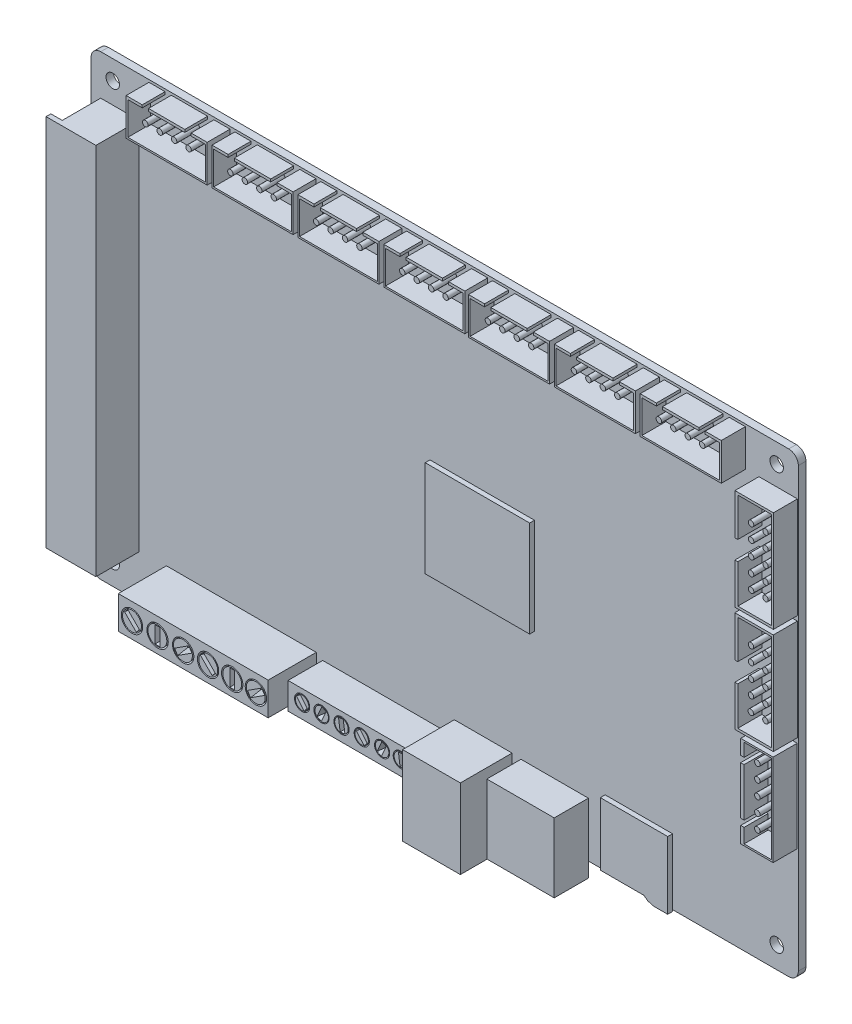
SolidWorks part; units mm, degrees
ref_plane "Front Plane" through (0, 0, 0) normal (0, 0, 1) x (1, 0, 0)
ref_plane "Top Plane" through (0, 0, 0) normal (0, 1, 0) x (1, 0, 0)
ref_plane "Right Plane" through (0, 0, 0) normal (1, 0, 0) x (0, 0, -1)
sketch "Sketch3" plane through (0, 0, 0) normal (0, 0, 1) x (1, 0, 0)
  line L1 (-56.2922, 43.8866) -> (90.7078, 43.8866)
  line L2 (-56.2922, 43.8866) -> (-56.2922, -51.1134)
  line L3 (-56.2922, -51.1134) -> (90.7078, -51.1134)
  line L4 (90.7078, 43.8866) -> (90.7078, -51.1134)
  dimension "D1" = 147
  dimension "D2" = 95
extrude "Boss-Extrude5" add sketch "Sketch3" along normal blind 1.5748 contours L1 L4 L3 L2
sketch "Sketch6" plane through (0, 0, 1.5748) normal (0, 0, 1) x (1, 0, 0)
  line L0 (-56.2922, 43.8866) -> (-56.2922, -51.1134) construction
  line L1 (-56.2922, -51.1134) -> (90.7078, -51.1134) construction
  line L2 (90.7078, 43.8866) -> (90.7078, -51.1134) construction
  circle A7 centre (-51.7922, -46.6134) radius 1.4
  circle A8 centre (-51.7922, 39.8866) radius 1.4
  circle A9 centre (86.2078, -46.6134) radius 1.4
  circle A10 centre (86.2078, 39.8866) radius 1.4
  dimension "D3" = 4.5
  dimension "D5" = 138
  dimension "D1" = 2.8
  dimension "D2" = 4.5
  dimension "D4" = 86.5
  dimension "D6" = 4.5
  dimension "D7" = 4.5
extrude "Cut-Extrude2" cut sketch "Sketch6" against normal blind 1.5748 contours A8 | A9 | A7 | A10
fillet "Fillet6" radius 2 4 edges at (-56.2922, -51.1134, 0.7874) (90.7078, -51.1134, 0.7874) (-56.2922, 43.8866, 0.7874) (90.7078, 43.8866, 0.7874)
sketch "Sketch15" plane through (0, 0, 1.5748) normal (0, 0, 1) x (1, 0, 0)
  line L1 (14.1477, 4.6258) -> (35.8627, 4.6258)
  line L2 (14.1477, 4.6258) -> (14.1477, -15.3707)
  line L3 (14.1477, -15.3707) -> (35.8627, -15.3707)
  line L4 (35.8627, 4.6258) -> (35.8627, -15.3707)
extrude "Boss-Extrude10" add sketch "Sketch15" along normal blind 1
sketch "Sketch7" plane through (0, 0, 1.5748) normal (0, 0, 1) x (1, 0, 0)
  line L0 (-54.2922, -51.1134) -> (88.7078, -51.1134) construction
  line L1 (19.2078, -39.6134) -> (31.2078, -39.6134)
  line L2 (19.2078, -39.6134) -> (19.2078, -56.1134)
  line L3 (19.2078, -56.1134) -> (31.2078, -56.1134)
  line L4 (31.2078, -39.6134) -> (31.2078, -56.1134)
  line L5 (-56.2922, 41.8866) -> (-56.2922, -49.1134) construction
  point P4 (25.2078, -39.6134)
  dimension "D1" = 16.5
  dimension "D2" = 12
  dimension "D3" = 5
  dimension "D4" = 75.5
extrude "Boss-Extrude6" add sketch "Sketch7" along normal blind 10.75
sketch "Sketch8" plane through (0, -56.1134, 0) normal (0, -1, 0) x (-1, 0, 0)
  line L0 (-22.3419, -10.6751) -> (-27.8419, -10.6751)
  line L1 (-22.3419, -10.6751) -> (-20.7873, -9.2035)
  line L2 (-27.8419, -10.6751) -> (-29.2373, -9.2011)
  line L3 (-20.7873, -9.2035) -> (-20.7873, -2.8951)
  line L4 (-20.7873, -2.8951) -> (-29.2373, -2.8951)
  line L5 (-29.2373, -2.8951) -> (-29.2373, -9.2011)
  dimension "D1" = 8.45
  dimension "D2" = 7.78
  dimension "D3" = 5.5
extrude "Cut-Extrude3" cut sketch "Sketch8" against normal blind 12
sketch "Sketch9" plane through (0, -44.1134, 0) normal (0, -1, 0) x (-1, 0, 0)
  line L1 (-22.3046, -8.5212) -> (-27.8046, -8.5212)
  line L2 (-22.3046, -8.5212) -> (-22.3046, -5.4712)
  line L3 (-22.3046, -5.4712) -> (-27.8046, -5.4712)
  line L4 (-27.8046, -8.5212) -> (-27.8046, -5.4712)
  dimension "D1" = 3.05
  dimension "D2" = 5.5
extrude "Boss-Extrude7" add sketch "Sketch9" along normal blind 11
sketch "Sketch10" plane through (0, 0, 1.5748) normal (0, 0, 1) x (1, 0, 0)
  line L1 (33.0644, -39.8012) -> (47.0644, -39.8012)
  line L2 (33.0644, -39.8012) -> (33.0644, -54.2012)
  line L3 (33.0644, -54.2012) -> (47.0644, -54.2012)
  line L4 (47.0644, -39.8012) -> (47.0644, -54.2012)
  dimension "D1" = 14.4
  dimension "D2" = 14
extrude "Boss-Extrude8" add sketch "Sketch10" along normal blind 7.1
sketch "Sketch13" plane through (0, -54.2012, 0) normal (0, -1, 0) x (1, 0, 0)
  line L1 (33.801, 7.7215) -> (46.301, 7.7215)
  line L2 (33.801, 7.7215) -> (33.801, 2.6215)
  line L3 (33.801, 2.6215) -> (46.301, 2.6215)
  line L4 (46.301, 7.7215) -> (46.301, 2.6215)
  dimension "D1" = 12.5
  dimension "D2" = 5.1
extrude "Cut-Extrude4" cut sketch "Sketch13" against normal blind 13.1
sketch "Sketch14" plane through (0, -41.1012, 0) normal (0, -1, 0) x (1, 0, 0)
  line L1 (34.0885, 7.335) -> (46.0885, 7.335)
  line L2 (34.0885, 7.335) -> (34.0885, 5.335)
  line L3 (34.0885, 5.335) -> (46.0885, 5.335)
  line L4 (46.0885, 7.335) -> (46.0885, 5.335)
  dimension "D1" = 12
  dimension "D2" = 2
extrude "Boss-Extrude9" add sketch "Sketch14" along normal blind 13.1
sketch "Sketch17" plane through (0, 0, 1.5748) normal (0, 0, 1) x (1, 0, 0)
  line L0 (50.553, -50.5188) -> (59.5882, -50.5188)
  line L1 (50.553, -37.4607) -> (64.553, -37.4607)
  line L2 (50.553, -37.4607) -> (50.553, -50.5188)
  line L3 (61.5418, -51.4607) -> (64.553, -51.4607)
  line L4 (64.553, -37.4607) -> (64.553, -51.4607)
  line L5 (59.5882, -50.5188) -> (60.4255, -51.1134)
  line L6 (47.0644, -51.1134) -> (88.7078, -51.1134) construction
  line L7 (60.4255, -51.1134) -> (61.5418, -51.4607)
  dimension "D1" = 14
  dimension "D2" = 14
extrude "Boss-Extrude12" add sketch "Sketch17" along normal blind 1
sketch "Sketch18" plane through (0, -50.5188, 0) normal (0, -1, 0) x (-1, 0, 0)
  line L1 (-50.8215, -2.3946) -> (-59.6018, -2.3946)
  line L2 (-50.8215, -2.3946) -> (-50.8215, -1.7409)
  line L3 (-50.8215, -1.7409) -> (-59.6018, -1.7409)
  line L4 (-59.6018, -2.3946) -> (-59.6018, -1.7409)
extrude "Cut-Extrude6" cut sketch "Sketch18" against normal blind 12
sketch "Sketch20" plane through (59.6018, 0, 0) normal (-1, 0, 0) x (0, 0, 1)
  line L0 (1.7409, -50.5188) -> (2.3946, -50.5188) construction
  line L1 (2.3635, -38.552) -> (1.7409, -38.552)
  line L2 (2.3635, -38.552) -> (2.3635, -50.5188)
  line L3 (2.3635, -50.5188) -> (1.7409, -50.5188)
  line L4 (1.7409, -38.552) -> (1.7409, -50.5188)
  line L5 (1.7409, -38.5188) -> (1.7409, -50.5188) construction
extrude "Cut-Extrude10" cut sketch "Sketch20" against normal blind 4.2
sketch "Sketch23" plane through (-3.8693, -5.4478, 0) normal (-0.5791, -0.8153, 0) x (0.8153, -0.5791, 0)
  line L0 (77.8348, 2.3946) -> (77.8348, 1.7409) construction
  line L1 (77.8348, 2.3894) -> (78.8617, 2.3894)
  line L2 (77.8348, 2.3894) -> (77.8348, 1.7571)
  line L3 (77.8348, 1.7571) -> (78.8617, 1.7571)
  line L4 (78.8617, 2.3894) -> (78.8617, 1.7571)
  line L5 (78.8617, 2.5748) -> (78.8617, 1.5748) construction
extrude "Cut-Extrude11" cut sketch "Sketch23" against normal blind 6.2
sketch "Sketch24" plane through (-9.1658, -29.4664, 0) normal (-0.297, -0.9549, 0) x (0.9549, -0.297, 0)
  line L0 (74.0494, 2.5748) -> (74.0494, 1.5748) construction
  line L1 (72.8803, 2.3894) -> (74.0494, 2.3894)
  line L2 (72.8803, 2.3894) -> (72.8803, 1.7551)
  line L3 (72.8803, 1.7551) -> (74.0494, 1.7551)
  line L4 (74.0494, 2.3894) -> (74.0494, 1.7551)
extrude "Cut-Extrude12" cut sketch "Sketch24" against normal blind 7.2
sketch "Sketch25" plane through (0, -51.4607, 0) normal (0, -1, 0) x (1, 0, 0)
  line L1 (61.5418, 2.3894) -> (64.4593, 2.3894)
  line L2 (61.5418, 2.3894) -> (61.5418, 1.7551)
  line L3 (61.5418, 1.7551) -> (64.4593, 1.7551)
  line L4 (64.4593, 2.3894) -> (64.4593, 1.7551)
extrude "Cut-Extrude13" cut sketch "Sketch25" against normal blind 12.2
sketch "Sketch26" plane through (0, 0, 1.5748) normal (0, 0, 1) x (1, 0, 0)
  line L1 (17.0307, -48.1542) -> (-8.1581, -48.1542)
  line L2 (17.0307, -48.1542) -> (17.0307, -42.6208)
  line L3 (17.0307, -42.6208) -> (-8.1581, -42.6208)
  line L4 (-8.1581, -48.1542) -> (-8.1581, -42.6208)
extrude "Boss-Extrude13" add sketch "Sketch26" along normal blind 7.2
sketch "Sketch27" plane through (0, 0, 8.7748) normal (0, 0, 1) x (1, 0, 0)
  circle A0 centre (-5.2362, -45.1806) radius 1.5803
  circle A1 centre (-1.2032, -45.1806) radius 1.5803
  circle A2 centre (2.957, -45.1806) radius 1.5803
  circle A3 centre (7.1668, -45.1908) radius 1.5803
  circle A4 centre (11.4, -45.1908) radius 1.5803
  circle A5 centre (15.2791, -45.1908) radius 1.5803
extrude "Cut-Extrude15" cut sketch "Sketch27" against normal blind 6.2
sketch "Sketch29" plane through (0, -48.1542, 0) normal (0, -1, 0) x (1, 0, 0)
  line L0 (-8.1581, 5.1748) -> (17.0307, 5.1748) construction
  line L1 (-8.1581, 8.7748) -> (-8.1581, 1.5748) construction
  line L2 (17.0307, 8.7748) -> (17.0307, 1.5748) construction
  line L3 (-7.6895, 11.9968) -> (-7.6895, 5.1748) construction
  line L4 (-3.9145, 11.9968) -> (-3.9145, 5.1748) construction
  line L5 (-3.487, 5.1563) -> (0.1391, 5.1563)
  line L6 (-7.6895, 5.1707) -> (-3.9145, 5.1707)
  line L7 (-7.6895, 5.1707) -> (-7.6895, 1.9056)
  line L8 (-7.6895, 1.9056) -> (-3.9145, 1.9056)
  line L9 (-3.9145, 5.1707) -> (-3.9145, 1.9056)
  line L10 (-3.487, 5.1563) -> (-3.487, 1.8334)
  line L11 (-3.487, 1.8334) -> (0.1391, 1.8334)
  line L12 (0.1391, 5.1563) -> (0.1391, 1.8334)
  line L13 (0.772, 5.2105) -> (4.4078, 5.2105)
  line L14 (0.772, 5.2105) -> (0.772, 1.8519)
  line L15 (0.772, 1.8519) -> (4.4078, 1.8519)
  line L16 (4.4078, 5.2105) -> (4.4078, 1.8519)
  line L17 (5.1003, 5.1709) -> (8.7885, 5.1709)
  line L18 (5.1003, 5.1709) -> (5.1003, 1.8362)
  line L19 (5.1003, 1.8362) -> (8.7885, 1.8362)
  line L20 (8.7885, 5.1709) -> (8.7885, 1.8362)
  line L21 (9.3884, 5.192) -> (12.9675, 5.192)
  line L22 (9.3884, 5.192) -> (9.3884, 1.8436)
  line L23 (9.3884, 1.8436) -> (12.9675, 1.8436)
  line L24 (12.9675, 5.192) -> (12.9675, 1.8436)
  line L25 (13.3889, 5.2027) -> (16.8771, 5.2027)
  line L26 (13.3889, 5.2027) -> (13.3889, 1.8194)
  line L27 (13.3889, 1.8194) -> (16.8771, 1.8194)
  line L28 (16.8771, 5.2027) -> (16.8771, 1.8194)
extrude "Cut-Extrude18" cut sketch "Sketch29" against normal blind 5.2
sketch "Sketch39" plane through (0, 0, 8.7748) normal (0, 0, 1) x (1, 0, 0)
  circle A0 centre (-5.2362, -45.1806) radius 1.3961
  circle A1 centre (-1.1593, -45.1806) radius 1.3961
  circle A3 centre (2.9415, -45.1806) radius 1.3961
  circle A4 centre (7.1495, -45.1806) radius 1.3961
  circle A5 centre (11.4024, -45.1806) radius 1.3961
  circle A6 centre (15.2907, -45.1806) radius 1.3961
extrude "Boss-Extrude19" add sketch "Sketch39" against normal blind 6 draft 2 separate body
sketch "Sketch89" plane through (0, -48.1542, 0) normal (0, -1, 0) x (1, 0, 0)
  line L0 (-3.9145, 1.9056) -> (-3.9145, 5.1707) construction
  line L1 (-7.6895, 5.1707) -> (-3.9145, 5.1707)
  line L2 (-7.6895, 5.1707) -> (-7.6895, 2.6391)
  line L3 (-7.6895, 2.6391) -> (-3.9145, 2.6391)
  line L4 (-3.9145, 5.1707) -> (-3.9145, 2.6391)
  line L5 (0.1391, 1.8334) -> (0.1391, 5.1563) construction
  line L6 (-3.487, 5.1563) -> (0.1391, 5.1563)
  line L7 (-3.487, 5.1563) -> (-3.487, 2.6391)
  line L8 (-3.487, 2.6391) -> (0.1391, 2.6391)
  line L9 (0.1391, 5.1563) -> (0.1391, 2.6391)
  line L10 (4.4078, 1.8519) -> (4.4078, 5.2105) construction
  line L11 (0.772, 5.2105) -> (4.4078, 5.2105)
  line L12 (0.772, 5.2105) -> (0.772, 2.6391)
  line L13 (0.772, 2.6391) -> (4.4078, 2.6391)
  line L14 (4.4078, 5.2105) -> (4.4078, 2.6391)
  line L15 (8.7885, 1.8362) -> (8.7885, 5.1709) construction
  line L16 (5.1003, 5.1709) -> (8.7885, 5.1709)
  line L17 (5.1003, 5.1709) -> (5.1003, 2.6391)
  line L18 (5.1003, 2.6391) -> (8.7885, 2.6391)
  line L19 (8.7885, 5.1709) -> (8.7885, 2.6391)
  line L20 (12.9675, 1.8436) -> (12.9675, 5.192) construction
  line L21 (9.3884, 5.192) -> (12.9675, 5.192)
  line L22 (9.3884, 5.192) -> (9.3884, 2.6451)
  line L23 (9.3884, 2.6451) -> (12.9675, 2.6451)
  line L24 (12.9675, 5.192) -> (12.9675, 2.6451)
  line L25 (16.8771, 1.8194) -> (16.8771, 5.2027) construction
  line L26 (13.3889, 5.2027) -> (16.8771, 5.2027)
  line L27 (13.3889, 5.2027) -> (13.3889, 2.6451)
  line L28 (13.3889, 2.6451) -> (16.8771, 2.6451)
  line L29 (16.8771, 5.2027) -> (16.8771, 2.6451)
extrude "Boss-Extrude42" add sketch "Sketch89" along normal blind 0.001 separate body
sketch "Sketch88" plane through (0, 0, 8.7748) normal (0, 0, 1) x (1, 0, 0)
  line L0 (-5.2362, -43.7845) -> (-5.2362, -46.5768) construction
  line L1 (-6.6324, -45.1806) -> (-3.8401, -45.1806) construction
  line L2 (-2.5554, -45.1806) -> (0.2369, -45.1806) construction
  line L3 (-1.1593, -43.7845) -> (-1.1593, -46.5768) construction
  line L4 (2.9415, -43.7845) -> (2.9415, -46.5768) construction
  line L5 (4.3376, -45.1806) -> (1.5453, -45.1806) construction
  line L6 (7.2235, -43.8158) -> (7.2235, -46.6081) construction
  line L7 (5.8274, -45.212) -> (8.6197, -45.212) construction
  line L8 (9.9043, -45.212) -> (12.6966, -45.212) construction
  line L9 (11.3005, -43.8158) -> (11.3005, -46.6081) construction
  line L10 (15.4012, -43.8158) -> (15.4012, -46.6081) construction
  line L11 (16.7974, -45.212) -> (14.0051, -45.212) construction
  line L12 (-6.4146, -44.5249) -> (-5.6454, -43.886)
  line L13 (-5.6454, -43.886) -> (-4.0481, -45.8092)
  line L14 (-4.0481, -45.8092) -> (-4.8173, -46.4481)
  line L15 (-6.4146, -44.5249) -> (-4.8173, -46.4481)
  line L25 (2.3257, -44.0173) -> (3.316, -43.8781)
  line L26 (-1.1161, -43.833) -> (-0.2026, -44.2397)
  line L27 (-1.1161, -43.833) -> (-2.133, -46.1169)
  line L28 (-2.133, -46.1169) -> (-1.2194, -46.5236)
  line L29 (-0.2026, -44.2397) -> (-1.2194, -46.5236)
  line L30 (2.3257, -44.0173) -> (2.6736, -46.493)
  line L31 (2.6736, -46.493) -> (3.6639, -46.3538)
  line L32 (3.316, -43.8781) -> (3.6639, -46.3538)
  line L33 (6.0451, -44.5562) -> (6.8144, -43.9173)
  line L34 (6.8144, -43.9173) -> (8.4117, -45.8405)
  line L35 (8.4117, -45.8405) -> (7.6424, -46.4794)
  line L36 (6.0451, -44.5562) -> (7.6424, -46.4794)
  line L37 (14.7854, -44.0487) -> (15.7757, -43.9095)
  line L38 (11.3436, -43.8644) -> (12.2572, -44.2711)
  line L39 (11.3436, -43.8644) -> (10.3268, -46.1482)
  line L40 (10.3268, -46.1482) -> (11.2403, -46.555)
  line L41 (12.2572, -44.2711) -> (11.2403, -46.555)
  line L42 (14.7854, -44.0487) -> (15.1334, -46.5243)
  line L43 (15.1334, -46.5243) -> (16.1236, -46.3852)
  line L44 (15.7757, -43.9095) -> (16.1236, -46.3852)
  circle A0 centre (-5.2362, -45.1806) radius 1.3961 construction
  circle A1 centre (-1.1593, -45.1806) radius 1.3961 construction
  circle A2 centre (2.9415, -45.1806) radius 1.3961 construction
  dimension "D1" = 1
  dimension "D2" = 2.5
  dimension "D3" = 1
  dimension "D4" = 2.5
  dimension "D5" = 2.5
  dimension "D6" = 1
  dimension "D7" = 2.5
extrude "Cut-Extrude45" cut sketch "Sketch88" against normal blind 2 draft 10
sketch "Sketch32" plane through (0, 0, 1.5748) normal (0, 0, 1) x (1, 0, 0)
  line L1 (-40.6347, -41.8254) -> (-9.4873, -41.8254)
  line L2 (-40.6347, -41.8254) -> (-40.6347, -48.6239)
  line L3 (-40.6347, -48.6239) -> (-9.4873, -48.6239)
  line L4 (-9.4873, -41.8254) -> (-9.4873, -48.6239)
extrude "Boss-Extrude16" add sketch "Sketch32" along normal blind 10
sketch "Sketch36" plane through (0, 0, 11.5748) normal (0, 0, 1) x (1, 0, 0)
  circle A0 centre (-37.7869, -45.3403) radius 2.2193
  circle A1 centre (-32.4689, -45.3403) radius 2.2193
  circle A2 centre (-27.1553, -45.3403) radius 2.2193
  circle A3 centre (-21.9801, -45.3403) radius 2.2193
  circle A4 centre (-16.9661, -45.3403) radius 2.2193
  circle A5 centre (-12.0376, -45.3403) radius 2.2193
extrude "Cut-Extrude19" cut sketch "Sketch36" against normal blind 6
sketch "Sketch37" plane through (0, -48.6239, 0) normal (0, -1, 0) x (1, 0, 0)
  line L0 (-35.8516, 12.9634) -> (-35.8516, 5.364) construction
  line L1 (-40.2247, 12.9634) -> (-40.2247, 5.364) construction
  line L3 (-40.2247, 6.2641) -> (-35.8516, 6.2641)
  line L4 (-40.2247, 6.2641) -> (-40.2247, 1.9915)
  line L5 (-40.2247, 1.9915) -> (-35.8516, 1.9915)
  line L6 (-35.8516, 6.2641) -> (-35.8516, 1.9915)
  line L10 (-34.4118, 12.4369) -> (-34.4118, 6.2641) construction
  line L11 (-30.0093, 12.4369) -> (-30.0093, 6.2641) construction
  line L12 (-29.0289, 12.4369) -> (-29.0289, 6.2641) construction
  line L13 (-24.7681, 12.4369) -> (-24.7681, 6.2641) construction
  line L14 (-23.8661, 12.4369) -> (-23.8661, 6.2641) construction
  line L15 (-19.5674, 12.4369) -> (-19.5674, 6.2641) construction
  line L16 (-18.895, 12.4369) -> (-18.895, 6.2641) construction
  line L17 (-14.6107, 12.4369) -> (-14.6107, 6.2641) construction
  line L18 (-14.0247, 12.4369) -> (-14.0247, 6.2641) construction
  line L19 (-9.7798, 12.4369) -> (-9.7798, 6.2641) construction
  line L20 (-34.6961, 6.278) -> (-30.323, 6.278)
  line L21 (-34.6961, 6.278) -> (-34.6961, 2.0054)
  line L22 (-34.6961, 2.0054) -> (-30.323, 2.0054)
  line L23 (-30.323, 6.278) -> (-30.323, 2.0054)
  line L24 (-29.4602, 6.2923) -> (-25.0871, 6.2923)
  line L25 (-29.4602, 6.2923) -> (-29.4602, 2.0197)
  line L26 (-29.4602, 2.0197) -> (-25.0871, 2.0197)
  line L27 (-25.0871, 6.2923) -> (-25.0871, 2.0197)
  line L28 (-24.2951, 6.2692) -> (-19.9219, 6.2692)
  line L29 (-24.2951, 6.2692) -> (-24.2951, 1.9966)
  line L30 (-24.2951, 1.9966) -> (-19.9219, 1.9966)
  line L31 (-19.9219, 6.2692) -> (-19.9219, 1.9966)
  line L32 (-19.2092, 6.317) -> (-14.836, 6.317)
  line L33 (-19.2092, 6.317) -> (-19.2092, 2.0444)
  line L34 (-19.2092, 2.0444) -> (-14.836, 2.0444)
  line L35 (-14.836, 6.317) -> (-14.836, 2.0444)
  line L36 (-14.2723, 6.3278) -> (-9.8992, 6.3278)
  line L37 (-14.2723, 6.3278) -> (-14.2723, 2.0552)
  line L38 (-14.2723, 2.0552) -> (-9.8992, 2.0552)
  line L39 (-9.8992, 6.3278) -> (-9.8992, 2.0552)
extrude "Cut-Extrude20" cut sketch "Sketch37" against normal blind 6
sketch "Sketch38" plane through (0, 0, 11.5748) normal (0, 0, 1) x (1, 0, 0)
  circle A0 centre (-37.7869, -45.3403) radius 1.9625
  circle A1 centre (-32.5144, -45.3403) radius 1.9625
  circle A2 centre (-27.2038, -45.3403) radius 1.9625
  circle A3 centre (-21.9437, -45.3403) radius 1.9625
  circle A4 centre (-16.9625, -45.3403) radius 1.9625
  circle A5 centre (-12.0677, -45.3403) radius 1.9625
extrude "Boss-Extrude18" add sketch "Sketch38" against normal blind 8.5 draft 4 separate body
sketch "Sketch86" plane through (0, 0, 11.5748) normal (0, 0, 1) x (1, 0, 0)
  line L0 (-39.3614, -44.4323) -> (-36.8865, -46.9071)
  line L1 (-36.8865, -46.9071) -> (-36.1794, -46.2)
  line L2 (-36.1794, -46.2) -> (-38.6543, -43.7252)
  line L3 (-38.6543, -43.7252) -> (-39.3614, -44.4323)
  line L4 (-37.7869, -43.3779) -> (-37.7869, -47.3028) construction
  line L5 (-37.7869, -45.3403) -> (-35.8245, -45.3403) construction
  line L6 (-35.8245, -45.3403) -> (-39.7494, -45.3403) construction
  line L7 (-32.5144, -43.3779) -> (-32.5144, -47.3028) construction
  line L8 (-33.0144, -43.5903) -> (-32.0144, -43.5903)
  line L9 (-33.0144, -43.5903) -> (-33.0144, -47.0903)
  line L10 (-33.0144, -47.0903) -> (-32.0144, -47.0903)
  line L11 (-32.0144, -43.5903) -> (-32.0144, -47.0903)
  line L12 (-34.4768, -45.3403) -> (-30.5519, -45.3403) construction
  line L13 (-29.1662, -45.3403) -> (-25.2413, -45.3403) construction
  line L14 (-27.2038, -43.3779) -> (-27.2038, -47.3028) construction
  line L15 (-28.9358, -45.7982) -> (-28.2923, -46.7982)
  line L16 (-28.2923, -46.7982) -> (-25.349, -44.9043)
  line L17 (-25.349, -44.9043) -> (-25.9924, -43.9043)
  line L18 (-25.9924, -43.9043) -> (-28.9358, -45.7982)
  line L19 (-23.5999, -44.3719) -> (-21.1251, -46.8467)
  line L20 (-21.1251, -46.8467) -> (-20.418, -46.1396)
  line L21 (-20.418, -46.1396) -> (-22.8928, -43.6647)
  line L22 (-22.8928, -43.6647) -> (-23.5999, -44.3719)
  line L23 (-22.0122, -43.3758) -> (-22.0122, -47.3048) construction
  line L24 (-22.0122, -45.3403) -> (-19.9813, -45.3403) construction
  line L25 (-19.9813, -45.3403) -> (-23.9062, -45.3403) construction
  line L26 (-16.9625, -43.3758) -> (-16.9625, -47.3028) construction
  line L27 (-17.4625, -43.5903) -> (-16.4625, -43.5903)
  line L28 (-17.4625, -43.5903) -> (-17.4625, -47.0903)
  line L29 (-17.4625, -47.0903) -> (-16.4625, -47.0903)
  line L30 (-16.4625, -43.5903) -> (-16.4625, -47.0903)
  line L31 (-18.9249, -45.3403) -> (-15, -45.3403) construction
  line L32 (-14.0154, -45.3714) -> (-10.0904, -45.3714) construction
  line L33 (-12.0529, -43.4089) -> (-12.0529, -47.3338) construction
  line L34 (-13.7849, -45.8293) -> (-13.1415, -46.8293)
  line L35 (-13.1415, -46.8293) -> (-10.1981, -44.9354)
  line L36 (-10.1981, -44.9354) -> (-10.8416, -43.9354)
  line L37 (-10.8416, -43.9354) -> (-13.7849, -45.8293)
  circle A0 centre (-37.7869, -45.3403) radius 1.9625 construction
  circle A1 centre (-32.5144, -45.3403) radius 1.9625 construction
  circle A2 centre (-27.2038, -45.3403) radius 1.9625 construction
  circle A6 centre (-16.9625, -45.3403) radius 1.9625 construction
  circle A7 centre (-21.9437, -45.3403) radius 1.9625 construction
  dimension "D1" = 3.5
  dimension "D2" = 1
  dimension "D3" = 3.5
  dimension "D4" = 1
  dimension "D5" = 3.5
  dimension "D6" = 1
  dimension "D7" = 3.5
  dimension "D8" = 1
  dimension "D9" = 3.5
  dimension "D10" = 1
  dimension "D11" = 3.5
  dimension "D12" = 1
extrude "Cut-Extrude44" cut sketch "Sketch86" against normal blind 2 draft 10
sketch "Sketch87" plane through (0, -48.6239, 0) normal (0, -1, 0) x (1, 0, 0)
  line L0 (-35.8516, 1.9915) -> (-35.8516, 6.2641) construction
  line L1 (-40.2247, 6.2641) -> (-35.8516, 6.2641)
  line L2 (-40.2247, 6.2641) -> (-40.2247, 3.2863)
  line L3 (-40.2247, 3.2863) -> (-35.8516, 3.2863)
  line L4 (-35.8516, 6.2641) -> (-35.8516, 3.2863)
  line L5 (-30.323, 2.0054) -> (-30.323, 6.278) construction
  line L6 (-34.6961, 6.278) -> (-30.323, 6.278)
  line L7 (-34.6961, 6.278) -> (-34.6961, 3.2863)
  line L8 (-34.6961, 3.2863) -> (-30.323, 3.2863)
  line L9 (-30.323, 6.278) -> (-30.323, 3.2863)
  line L10 (-25.0871, 2.0197) -> (-25.0871, 6.2923) construction
  line L11 (-29.4602, 6.2923) -> (-25.0871, 6.2923)
  line L12 (-29.4602, 6.2923) -> (-29.4602, 3.2863)
  line L13 (-29.4602, 3.2863) -> (-25.0871, 3.2863)
  line L14 (-25.0871, 6.2923) -> (-25.0871, 3.2863)
  line L15 (-19.9219, 1.9966) -> (-19.9219, 6.2692) construction
  line L16 (-24.2951, 6.2692) -> (-19.9219, 6.2692)
  line L17 (-24.2951, 6.2692) -> (-24.2951, 3.2863)
  line L18 (-24.2951, 3.2863) -> (-19.9219, 3.2863)
  line L19 (-19.9219, 6.2692) -> (-19.9219, 3.2863)
  line L20 (-14.836, 2.0444) -> (-14.836, 6.317) construction
  line L21 (-19.1947, 6.2692) -> (-14.836, 6.2692)
  line L22 (-19.1947, 6.2692) -> (-19.1947, 3.2863)
  line L23 (-19.1947, 3.2863) -> (-14.836, 3.2863)
  line L24 (-14.836, 6.2692) -> (-14.836, 3.2863)
  line L25 (-9.8992, 2.0552) -> (-9.8992, 6.3278) construction
  line L26 (-14.2723, 6.3278) -> (-9.8992, 6.3278)
  line L27 (-14.2723, 6.3278) -> (-14.2723, 3.2863)
  line L28 (-14.2723, 3.2863) -> (-9.8992, 3.2863)
  line L29 (-9.8992, 6.3278) -> (-9.8992, 3.2863)
extrude "Boss-Extrude41" add sketch "Sketch87" along normal blind 0.001 separate body
sketch "Sketch40" plane through (0, 0, 1.5748) normal (0, 0, 1) x (1, 0, 0)
  line L1 (83.7219, -27.2035) -> (90.4719, -27.2035)
  line L2 (83.7219, -27.2035) -> (83.7219, -8.2035)
  line L3 (83.7219, -8.2035) -> (90.4719, -8.2035)
  line L4 (90.4719, -27.2035) -> (90.4719, -8.2035)
  line L5 (82.5011, -7.2035) -> (90.5011, -7.2035)
  line L6 (82.5011, -7.2035) -> (82.5011, 13.7965)
  line L7 (82.5011, 13.7965) -> (90.5011, 13.7965)
  line L8 (90.5011, -7.2035) -> (90.5011, 13.7965)
  line L9 (82.5228, 14.7965) -> (90.5228, 14.7965)
  line L10 (82.5228, 14.7965) -> (82.5228, 35.7965)
  line L11 (82.5228, 35.7965) -> (90.5228, 35.7965)
  line L12 (90.5228, 14.7965) -> (90.5228, 35.7965)
  dimension "D1" = 21
  dimension "D2" = 21
  dimension "D3" = 8
  dimension "D4" = 8
  dimension "D5" = 19
  dimension "D6" = 6.75
  dimension "D7" = 1
  dimension "D8" = 1
extrude "Boss-Extrude20" add sketch "Sketch40" along normal blind 5
sketch "Sketch41" plane through (0, 0, 6.5748) normal (0, 0, 1) x (1, 0, 0)
  line L0 (83.1294, 15.2965) -> (90.1728, 15.2965)
  line L1 (83.1154, -6.7035) -> (90.1511, -6.7035)
  line L2 (83.1154, -6.7035) -> (83.1154, 13.2965)
  line L3 (83.1154, 13.2965) -> (90.1511, 13.2965)
  line L4 (90.1511, -6.7035) -> (90.1511, 13.2965)
  line L5 (83.1294, 15.2965) -> (83.1294, 35.2965)
  line L6 (83.1294, 35.2965) -> (90.1728, 35.2965)
  line L7 (90.1728, 15.2965) -> (90.1728, 35.2965)
  line L12 (82.5011, 1.2965) -> (83.1154, 1.2965)
  line L13 (84.4298, -26.8535) -> (90.1219, -26.8535)
  line L14 (84.4298, -26.8535) -> (84.4298, -8.5535)
  line L15 (84.4298, -8.5535) -> (90.1219, -8.5535)
  line L16 (90.1219, -26.8535) -> (90.1219, -8.5535)
  line L17 (82.5011, 13.7965) -> (82.5011, -7.2035) construction
  line L18 (83.1154, 1.2965) -> (83.1154, 5.2965)
  line L19 (83.1154, 5.2965) -> (82.5011, 5.2965)
  line L20 (82.5011, 13.7965) -> (82.5011, -7.2035) construction
  line L21 (82.5011, 5.2965) -> (82.5011, 1.2965)
  line L22 (83.1294, 23.2965) -> (82.5228, 23.2965)
  line L23 (82.5228, 35.7965) -> (82.5228, 14.7965) construction
  line L24 (82.5228, 23.2965) -> (82.5228, 27.2965)
  line L25 (82.5228, 27.2965) -> (83.1294, 27.2965)
  line L26 (83.1294, 27.2965) -> (83.1294, 23.2965)
  line L27 (84.4298, -23.8765) -> (83.7219, -23.8765)
  line L28 (83.7219, -23.8765) -> (83.7219, -22.5765)
  line L29 (83.7219, -22.5765) -> (84.4298, -22.5765)
  line L30 (84.4298, -11.2765) -> (83.7219, -11.2765)
  line L31 (83.7219, -11.2765) -> (83.7219, -12.5765)
  line L32 (83.7219, -12.5765) -> (84.4298, -12.5765)
  line L33 (83.7219, -8.2035) -> (83.7219, -27.2035) construction
  line L34 (83.7219, -27.2035) -> (90.4719, -27.2035) construction
  line L35 (90.4719, -27.2035) -> (90.4719, -8.2035) construction
  line L36 (90.4719, -8.2035) -> (83.7219, -8.2035) construction
  line L37 (82.5011, -7.2035) -> (90.5011, -7.2035) construction
  line L38 (90.5011, -7.2035) -> (90.5011, 13.7965) construction
  line L41 (90.5228, 14.7965) -> (90.5228, 35.7965) construction
  line L42 (90.5228, 35.7965) -> (82.5228, 35.7965) construction
  dimension "D1" = 4
  dimension "D2" = 4
  dimension "D3" = 1.3
  dimension "D4" = 1.3
  dimension "D5" = 10
  dimension "D6" = 0.35
  dimension "D7" = 0.35
  dimension "D8" = 0.35
  dimension "D9" = 8
  dimension "D10" = 8
  dimension "D11" = 0.5
  dimension "D12" = 0.35
  dimension "D13" = 8
  dimension "D14" = 8
  dimension "D15" = 0.35
  dimension "D16" = 0.5
extrude "Cut-Extrude24" cut sketch "Sketch41" against normal blind 5 contours L13 L16 L15 L14 | L29 L28 L27 L14 | L32 L31 L30 L14 | L1 L4 L3 L2 | L0 L7 L6 L5 | L21 L12 L18 L19 | L24 L25 L26 L22 region at (86.6511, 25.2965, 6.5748) region at (86.6333, 3.2965, 6.5748) region at (87.2758, -17.7035, 6.5748) region at (84.0758, -23.2265, 6.5748) region at (84.0758, -11.9265, 6.5748)
sketch "Sketch43" plane through (0, 0, 1.5748) normal (0, 0, 1) x (1, 0, 0)
  line L0 (83.1154, 5.2965) -> (83.1154, 13.2965) construction
  line L1 (83.1154, 13.2965) -> (90.1511, 13.2965) construction
  line L2 (83.1154, -6.7035) -> (90.1511, -6.7035) construction
  line L3 (84.4298, -22.5765) -> (84.4298, -12.5765) construction
  line L6 (83.1294, 27.2965) -> (83.1294, 35.2965) construction
  line L7 (83.1294, 35.2965) -> (90.1728, 35.2965) construction
  circle A0 centre (86.9298, -23.1879) radius 0.5691
  circle A1 centre (86.9298, -20.1879) radius 0.5691
  circle A2 centre (86.9298, -14.1879) radius 0.5691
  circle A3 centre (86.9298, -17.1879) radius 0.5691
  circle A4 centre (86.9298, -11.1879) radius 0.5691
  circle A5 centre (85.5717, -2.7035) radius 0.5691
  circle A6 centre (85.6154, 0.2965) radius 0.5691
  circle A7 centre (85.6154, 6.2965) radius 0.5691
  circle A8 centre (85.6154, 3.2965) radius 0.5691
  circle A9 centre (85.6154, 9.2965) radius 0.5691
  circle A10 centre (88.6154, -2.7035) radius 0.5691
  circle A11 centre (88.6154, 0.2965) radius 0.5691
  circle A12 centre (88.6154, 6.2965) radius 0.5691
  circle A13 centre (88.6154, 3.2965) radius 0.5691
  circle A14 centre (88.6154, 9.2965) radius 0.5691
  circle A15 centre (85.6294, 19.2965) radius 0.5691
  circle A16 centre (85.6294, 22.2965) radius 0.5691
  circle A17 centre (85.6294, 28.2965) radius 0.5691
  circle A18 centre (85.6294, 25.3224) radius 0.5691
  circle A19 centre (85.6294, 31.2965) radius 0.5691
  circle A20 centre (88.6294, 19.2965) radius 0.5691
  circle A21 centre (88.6294, 22.2965) radius 0.5691
  circle A22 centre (88.6294, 28.2965) radius 0.5691
  circle A23 centre (88.6294, 25.2965) radius 0.5691
  circle A24 centre (88.6294, 31.2965) radius 0.5691
  dimension "D1" = 2.5
  dimension "D2" = 3
  dimension "D3" = 3
  dimension "D4" = 3
  dimension "D5" = 3
  dimension "D6" = 3
  dimension "D7" = 3
  dimension "D8" = 4
  dimension "D9" = 3
  dimension "D10" = 3
  dimension "D11" = 4
  dimension "D12" = 3
  dimension "D13" = 3
  dimension "D14" = 3
  dimension "D15" = 3
  dimension "D16" = 2.5
  dimension "D17" = 4
  dimension "D18" = 3
  dimension "D19" = 3
  dimension "D20" = 3
  dimension "D21" = 2.5
  dimension "D22" = 3
  dimension "D23" = 3
  dimension "D24" = 3
extrude "Boss-Extrude23" add sketch "Sketch43" along normal blind 4.75
sketch "Sketch47" plane through (0, 0, 1.5748) normal (0, 0, 1) x (1, 0, 0)
  line L5 (61.838, 35.6866) -> (44.988, 35.6866)
  line L6 (61.838, 35.6866) -> (61.838, 43.3866)
  line L7 (61.838, 43.3866) -> (44.988, 43.3866)
  line L8 (44.988, 35.6866) -> (44.988, 43.3866)
  line L9 (43.988, 35.6866) -> (27.138, 35.6866)
  line L10 (43.988, 35.6866) -> (43.988, 43.3866)
  line L11 (43.988, 43.3866) -> (27.138, 43.3866)
  line L12 (27.138, 35.6866) -> (27.138, 43.3866)
  line L13 (79.688, 35.6866) -> (62.838, 35.6866)
  line L14 (79.688, 35.6866) -> (79.688, 43.3866)
  line L15 (79.688, 43.3866) -> (62.838, 43.3866)
  line L16 (62.838, 35.6866) -> (62.838, 43.3866)
  line L17 (-54.2922, 43.8866) -> (88.7078, 43.8866) construction
  dimension "D1" = 1
  dimension "D2" = 0.5
  dimension "D3" = 16.85
  dimension "D4" = 7.7
  dimension "D5" = 16.85
  dimension "D6" = 7.7
  dimension "D7" = 0.5
  dimension "D8" = 1
  dimension "D9" = 7.7
  dimension "D10" = 16.85
  dimension "D11" = 0.5
extrude "Boss-Extrude25" add sketch "Sketch47" along normal blind 5
sketch "Sketch48" plane through (0, 0, 6.5748) normal (0, 0, 1) x (1, 0, 0)
  line L0 (43.638, 36.0366) -> (27.488, 36.0366)
  line L5 (43.638, 36.0366) -> (43.638, 42.8366)
  line L6 (43.638, 42.8366) -> (27.488, 42.8366)
  line L7 (27.488, 36.0366) -> (27.488, 42.8366)
  line L12 (61.488, 36.0366) -> (45.338, 36.0366)
  line L13 (61.488, 36.0366) -> (61.488, 42.8366)
  line L14 (61.488, 42.8366) -> (45.338, 42.8366)
  line L15 (45.338, 36.0366) -> (45.338, 42.8366)
  line L16 (79.338, 36.0366) -> (63.189, 36.0366)
  line L17 (79.338, 36.0366) -> (79.338, 42.8366)
  line L18 (79.338, 42.8366) -> (63.189, 42.8366)
  line L19 (63.189, 36.0366) -> (63.189, 42.8366)
  line L20 (76.338, 42.8366) -> (76.338, 43.3866)
  line L21 (79.688, 43.3866) -> (62.838, 43.3866) construction
  line L22 (76.338, 43.3866) -> (75.038, 43.3866)
  line L23 (75.038, 43.3866) -> (75.038, 42.8366)
  line L24 (67.489, 42.8366) -> (67.489, 43.3866)
  line L25 (67.489, 43.3866) -> (66.189, 43.3866)
  line L26 (66.189, 43.3866) -> (66.189, 42.8366)
  line L27 (58.488, 42.8366) -> (58.488, 43.3866)
  line L28 (61.838, 43.3866) -> (44.988, 43.3866) construction
  line L29 (58.488, 43.3866) -> (57.188, 43.3866)
  line L30 (57.188, 43.3866) -> (57.188, 42.8366)
  line L31 (49.638, 42.8366) -> (49.638, 43.3866)
  line L32 (49.638, 43.3866) -> (48.338, 43.3866)
  line L33 (48.338, 43.3866) -> (48.338, 42.8366)
  line L34 (40.638, 42.8366) -> (40.638, 43.3866)
  line L35 (43.988, 43.3866) -> (27.138, 43.3866) construction
  line L36 (40.638, 43.3866) -> (39.338, 43.3866)
  line L37 (39.338, 43.3866) -> (39.338, 42.8366)
  line L38 (31.788, 42.8366) -> (31.788, 43.3866)
  line L39 (31.788, 43.3866) -> (30.488, 43.3866)
  line L40 (30.488, 43.3866) -> (30.488, 42.8366)
  line L41 (79.688, 35.6866) -> (79.688, 43.3866) construction
  line L43 (62.838, 35.6866) -> (79.688, 35.6866) construction
  line L45 (61.838, 35.6866) -> (61.838, 43.3866) construction
  line L46 (44.988, 35.6866) -> (61.838, 35.6866) construction
  line L49 (27.138, 35.6866) -> (43.988, 35.6866) construction
  line L52 (43.988, 35.6866) -> (43.988, 43.3866) construction
  line M14 (43.988, 43.3866) -> (27.138, 43.3866)
  dimension "D1" = 1.3
  dimension "D2" = 1.3
  dimension "D3" = 3
  dimension "D4" = 3
  dimension "D5" = 6.8
  dimension "D6" = 16.1489
  dimension "D7" = 16.15
  dimension "D8" = 3
  dimension "D9" = 3
  dimension "D10" = 7.55
  dimension "D11" = 1.3
  dimension "D12" = 16.15
  dimension "D13" = 7.55
  dimension "D14" = 3
  dimension "D15" = 3
  dimension "D16" = 1.3
  dimension "D17" = 0.35
  dimension "D18" = 0.35
  dimension "D19" = 0.35
  dimension "D20" = 6.8
  dimension "D21" = 0.35
  dimension "D22" = 1.3
  dimension "D23" = 6.8
  dimension "D24" = 0.35
  dimension "D25" = 0.35
extrude "Cut-Extrude26" cut sketch "Sketch48" against normal blind 5 contours L7 L0 L5 L6 | L40 L6 L38 M14 | L37 L6 L34 M14 | L15 L12 L13 L14 | L32 L33 L14 L31 | L29 L30 L14 L27 | L19 L16 L17 L18 | L25 L26 L18 L24 | L22 L23 L18 L20 region at (35.563, 39.4366, 6.5748) region at (39.988, 43.1116, 6.5748) region at (31.138, 43.1116, 6.5748) region at (53.413, 39.4366, 6.5748) region at (57.838, 43.1116, 6.5748) region at (48.988, 43.1116, 6.5748) region at (71.2635, 39.4366, 6.5748) region at (75.688, 43.1116, 6.5748) region at (66.839, 43.1116, 6.5748)
sketch "Sketch50" plane through (0, 0, 1.5748) normal (0, 0, 1) x (1, 0, 0)
  line L1 (57.188, 42.8366) -> (49.638, 42.8366) construction
  line L3 (75.038, 42.8366) -> (67.489, 42.8366) construction
  line L4 (39.338, 42.8366) -> (31.788, 42.8366) construction
  circle A16 centre (69.4669, 40.3369) radius 0.5691
  circle A17 centre (66.4669, 40.3372) radius 0.5691
  circle A18 centre (72.4669, 40.3366) radius 0.5691
  circle A19 centre (75.4669, 40.3377) radius 0.5691
  circle A20 centre (51.8192, 40.3366) radius 0.5691
  circle A21 centre (48.8192, 40.3366) radius 0.5691
  circle A22 centre (54.8192, 40.3366) radius 0.5691
  circle A23 centre (57.8192, 40.3366) radius 0.5691
  circle A24 centre (33.9262, 40.3366) radius 0.5691
  circle A25 centre (30.9262, 40.3366) radius 0.5691
  circle A26 centre (36.9262, 40.3366) radius 0.5691
  circle A27 centre (39.9262, 40.3366) radius 0.5691
  dimension "D13" = 3
  dimension "D2" = 2.5
  dimension "D3" = 2.5
  dimension "D4" = 3
  dimension "D5" = 3
  dimension "D6" = 3
  dimension "D7" = 2.5
  dimension "D8" = 3
  dimension "D9" = 3
  dimension "D10" = 3
  dimension "D11" = 3
  dimension "D12" = 3
extrude "Boss-Extrude26" add sketch "Sketch50" along normal blind 4.75
sketch "Sketch51" plane through (0, 0, 1.5748) normal (0, 0, 1) x (1, 0, 0)
  line L0 (8.288, 35.6866) -> (-8.562, 35.6866)
  line L1 (8.288, 35.6866) -> (8.288, 43.3866)
  line L2 (8.288, 43.3866) -> (-8.562, 43.3866)
  line L3 (-8.562, 35.6866) -> (-8.562, 43.3866)
  line L8 (26.138, 35.6866) -> (9.288, 35.6866)
  line L9 (26.138, 35.6866) -> (26.138, 43.3866)
  line L10 (26.138, 43.3866) -> (9.288, 43.3866)
  line L11 (9.288, 35.6866) -> (9.288, 43.3866)
  line L12 (27.138, 43.3866) -> (27.138, 35.6866) construction
  line L13 (-54.2922, 43.8866) -> (88.7078, 43.8866) construction
  line L14 (-54.2922, 43.8866) -> (88.7078, 43.8866) construction
  dimension "D1" = 16.85
  dimension "D2" = 7.7
  dimension "D3" = 0.5
  dimension "D4" = 7.7
  dimension "D5" = 1
  dimension "D6" = 16.85
  dimension "D7" = 1
  dimension "D8" = 0.5
extrude "Boss-Extrude27" add sketch "Sketch51" along normal blind 4.75
sketch "Sketch52" plane through (0, 0, 6.3248) normal (0, 0, 1) x (1, 0, 0)
  line L4 (7.938, 36.0366) -> (-8.212, 36.0366)
  line L5 (7.938, 36.0366) -> (7.938, 42.8366)
  line L6 (7.938, 42.8366) -> (-8.212, 42.8366)
  line L7 (-8.212, 36.0366) -> (-8.212, 42.8366)
  line L8 (25.7869, 36.0366) -> (9.638, 36.0366)
  line L9 (25.7869, 36.0366) -> (25.7869, 42.8366)
  line L10 (25.7869, 42.8366) -> (9.638, 42.8366)
  line L11 (9.638, 36.0366) -> (9.638, 42.8366)
  line L12 (22.7869, 42.8366) -> (22.7869, 43.4897)
  line L13 (22.7869, 43.4897) -> (21.4869, 43.4897)
  line L14 (21.4869, 43.4897) -> (21.4869, 42.8366)
  line L15 (13.938, 42.8366) -> (13.938, 43.4897)
  line L16 (13.938, 43.4897) -> (12.638, 43.4897)
  line L17 (12.638, 43.4897) -> (12.638, 42.8366)
  line L18 (4.938, 42.8366) -> (4.938, 43.4124)
  line L19 (4.938, 43.4124) -> (3.638, 43.4124)
  line L20 (3.638, 43.4124) -> (3.638, 42.8366)
  line L21 (-3.912, 42.8366) -> (-3.912, 43.4173)
  line L22 (-3.912, 43.4173) -> (-5.212, 43.4173)
  line L23 (-5.212, 43.4173) -> (-5.212, 42.8366)
  line L24 (-8.562, 35.6866) -> (8.288, 35.6866) construction
  line L25 (-8.562, 43.3866) -> (-8.562, 35.6866) construction
  line L26 (9.288, 43.3866) -> (9.288, 35.6866) construction
  line L27 (9.288, 35.6866) -> (26.138, 35.6866) construction
  line M14 (8.288, 43.3866) -> (-8.562, 43.3866)
  dimension "D1" = 1.3
  dimension "D2" = 1.3
  dimension "D3" = 3
  dimension "D4" = 3
  dimension "D5" = 6.8
  dimension "D6" = 16.1489
  dimension "D7" = 16.15
  dimension "D8" = 3
  dimension "D9" = 3
  dimension "D10" = 7.55
  dimension "D11" = 1.3
  dimension "D12" = 0.35
  dimension "D13" = 0.35
  dimension "D14" = 0.35
  dimension "D15" = 0.35
  dimension "D18" = 6.8
extrude "Cut-Extrude28" cut sketch "Sketch52" against normal blind 4.75 contours L20 L6 L18 M14 | L7 L4 L5 L6 | L23 L6 L21 M14 | L11 L8 L9 L10 | L16 L17 L10 L15 | L13 L14 L10 L12 region at (-0.137, 39.4366, 6.3248) region at (4.288, 43.1116, 6.3248) region at (-4.562, 43.1116, 6.3248) region at (17.7124, 39.4366, 6.3248) region at (22.1369, 43.1631, 6.3248) region at (13.288, 43.1631, 6.3248)
sketch "Sketch53" plane through (0, 0, 1.5748) normal (0, 0, 1) x (1, 0, 0)
  line L0 (3.638, 42.8366) -> (-3.912, 42.8366) construction
  line L2 (21.4869, 42.8366) -> (13.938, 42.8366) construction
  circle A0 centre (16.1305, 40.3366) radius 0.5691
  circle A1 centre (13.1305, 40.3366) radius 0.5691
  circle A2 centre (19.1305, 40.3366) radius 0.5691
  circle A3 centre (22.1305, 40.3366) radius 0.5691
  circle A4 centre (-1.7625, 40.3366) radius 0.5691
  circle A5 centre (-4.7625, 40.3366) radius 0.5691
  circle A6 centre (1.2375, 40.3366) radius 0.5691
  circle A7 centre (4.2375, 40.3366) radius 0.5691
  dimension "D1" = 3
  dimension "D2" = 3
  dimension "D3" = 3
  dimension "D4" = 3
  dimension "D5" = 3
  dimension "D6" = 3
  dimension "D7" = 2.5
  dimension "D8" = 2.5
extrude "Boss-Extrude28" add sketch "Sketch53" along normal blind 4.75
sketch "Sketch54" plane through (0, 0, 1.5748) normal (0, 0, 1) x (1, 0, 0)
  line L0 (-9.562, 35.6866) -> (-26.412, 35.6866)
  line L1 (-9.562, 35.6866) -> (-9.562, 43.3866)
  line L2 (-9.562, 43.3866) -> (-26.412, 43.3866)
  line L3 (-26.412, 35.6866) -> (-26.412, 43.3866)
  line L4 (-54.2922, 43.8866) -> (88.7078, 43.8866) construction
  line L5 (-8.562, 43.3866) -> (-8.562, 35.6866) construction
  dimension "D1" = 16.85
  dimension "D2" = 7.7
  dimension "D3" = 0.5
  dimension "D4" = 1
extrude "Boss-Extrude29" add sketch "Sketch54" along normal blind 4.75
sketch "Sketch55" plane through (0, 0, 6.3248) normal (0, 0, 1) x (1, 0, 0)
  line L0 (-9.912, 36.0366) -> (-26.062, 36.0366)
  line L1 (-9.912, 36.0366) -> (-9.912, 42.8366)
  line L2 (-9.912, 42.8366) -> (-26.062, 42.8366)
  line L3 (-26.062, 36.0366) -> (-26.062, 42.8366)
  line L4 (-12.912, 42.8366) -> (-12.912, 43.6281)
  line L5 (-12.912, 43.6281) -> (-14.212, 43.6281)
  line L6 (-14.212, 43.6281) -> (-14.212, 42.8366)
  line L7 (-21.762, 42.8366) -> (-21.762, 43.6607)
  line L8 (-21.762, 43.6607) -> (-23.062, 43.6607)
  line L9 (-23.062, 43.6607) -> (-23.062, 42.8366)
  line L10 (-26.412, 43.3866) -> (-26.412, 35.6866) construction
  line L11 (-26.412, 35.6866) -> (-9.562, 35.6866) construction
  line M7 (-9.562, 43.3866) -> (-26.412, 43.3866)
  dimension "D1" = 16.15
  dimension "D2" = 3
  dimension "D3" = 3
  dimension "D4" = 7.55
  dimension "D5" = 1.3
  dimension "D6" = 6.8
  dimension "D7" = 0.35
  dimension "D8" = 0.35
extrude "Cut-Extrude29" cut sketch "Sketch55" against normal blind 4.75 contours L3 L0 L1 L2 | L9 L2 L7 M7 | L6 L2 L4 M7 region at (-17.987, 39.4366, 6.3248) region at (-13.562, 43.1116, 6.3248) region at (-22.412, 43.1116, 6.3248)
sketch "Sketch56" plane through (0, 0, 1.5748) normal (0, 0, 1) x (1, 0, 0)
  line L0 (-14.212, 42.8366) -> (-21.762, 42.8366) construction
  circle A0 centre (-19.5804, 40.3366) radius 0.5691
  circle A1 centre (-22.5804, 40.3366) radius 0.5691
  circle A2 centre (-16.5804, 40.3366) radius 0.5691
  circle A3 centre (-13.5804, 40.3366) radius 0.5691
  dimension "D1" = 3
  dimension "D2" = 3
  dimension "D3" = 3
  dimension "D4" = 2.5
extrude "Boss-Extrude30" add sketch "Sketch56" along normal blind 4.75
sketch "Sketch60" plane through (0, 0, 1.5748) normal (0, 0, 1) x (1, 0, 0)
  line L0 (-27.412, 35.6866) -> (-44.262, 35.6866)
  line L1 (-27.412, 35.6866) -> (-27.412, 43.3866)
  line L2 (-27.412, 43.3866) -> (-44.262, 43.3866)
  line L3 (-44.262, 35.6866) -> (-44.262, 43.3866)
  line L4 (-26.412, 43.3866) -> (-26.412, 35.6866) construction
  line L5 (-54.2922, 43.8866) -> (88.7078, 43.8866) construction
  dimension "D1" = 16.85
  dimension "D2" = 7.7
  dimension "D3" = 1
  dimension "D4" = 0.5
extrude "Boss-Extrude32" add sketch "Sketch60" along normal blind 4.75
sketch "Sketch61" plane through (0, 0, 6.3248) normal (0, 0, 1) x (1, 0, 0)
  line L0 (-27.762, 36.0366) -> (-43.912, 36.0366)
  line L1 (-27.762, 36.0366) -> (-27.762, 42.8366)
  line L2 (-27.762, 42.8366) -> (-43.912, 42.8366)
  line L3 (-43.912, 36.0366) -> (-43.912, 42.8366)
  line L4 (-30.762, 42.8366) -> (-30.762, 43.6281)
  line L5 (-30.762, 43.6281) -> (-32.062, 43.6281)
  line L6 (-32.062, 43.6281) -> (-32.062, 42.8366)
  line L7 (-39.612, 42.8366) -> (-39.612, 43.6607)
  line L8 (-39.612, 43.6607) -> (-40.912, 43.6607)
  line L9 (-40.912, 43.6607) -> (-40.912, 42.8366)
  line L10 (-44.262, 35.6866) -> (-27.412, 35.6866) construction
  line L11 (-44.262, 43.3866) -> (-44.262, 35.6866) construction
  line M6 (-27.412, 43.3866) -> (-44.262, 43.3866)
  dimension "D1" = 16.15
  dimension "D2" = 3
  dimension "D3" = 3
  dimension "D4" = 7.55
  dimension "D5" = 1.3
  dimension "D6" = 0.35
  dimension "D7" = 0.35
  dimension "D8" = 6.8
extrude "Cut-Extrude30" cut sketch "Sketch61" against normal blind 4.75 contours L3 L0 L1 L2 | L6 L2 L4 M6 | L9 L2 L7 M6 region at (-35.837, 39.4366, 6.3248) region at (-31.412, 43.1116, 6.3248) region at (-40.262, 43.1116, 6.3248)
sketch "Sketch62" plane through (0, 0, 1.5748) normal (0, 0, 1) x (1, 0, 0)
  line L0 (-32.062, 42.8366) -> (-39.612, 42.8366) construction
  circle A0 centre (-37.2811, 40.3366) radius 0.5691
  circle A1 centre (-40.2811, 40.3366) radius 0.5691
  circle A2 centre (-34.2811, 40.3366) radius 0.5691
  circle A3 centre (-31.2811, 40.3366) radius 0.5691
  dimension "D1" = 2.5
  dimension "D2" = 3
  dimension "D3" = 3
  dimension "D4" = 3
extrude "Boss-Extrude33" add sketch "Sketch62" along normal blind 4.75
sketch "Sketch16" plane through (0, 0, 1.5748) normal (0, 0, 1) x (1, 0, 0)
  line L0 (-56.2922, 41.8866) -> (-56.2922, -49.1134) construction
  line L1 (-54.2922, 35.5199) -> (-46.2922, 35.5199)
  line L2 (-54.2922, 35.5199) -> (-54.2922, -42.1228)
  line L3 (-54.2922, -42.1228) -> (-46.2922, -42.1228)
  line L4 (-46.2922, 35.5199) -> (-46.2922, -42.1228)
  dimension "D1" = 2
  dimension "D2" = 8
extrude "Boss-Extrude11" add sketch "Sketch16" along normal blind 8
sketch "Sketch64" plane through (-54.2922, 0, 0) normal (-1, 0, 0) x (0, 0, 1)
  line L0 (9.5748, 35.5199) -> (9.5748, -42.1228) construction
  line L1 (9.5748, 34.0199) -> (5.5748, 34.0199)
  line L2 (9.5748, 34.0199) -> (9.5748, 26.0199)
  line L3 (9.5748, 26.0199) -> (5.5748, 26.0199)
  line L4 (5.5748, 34.0199) -> (5.5748, 26.0199)
  line L41 (9.5748, 24.5199) -> (5.5748, 24.5199)
  line L42 (9.5748, 24.5199) -> (9.5748, 16.5199)
  line L43 (9.5748, 16.5199) -> (5.5748, 16.5199)
  line L44 (5.5748, 24.5199) -> (5.5748, 16.5199)
  line L45 (9.5748, 15.0199) -> (5.5748, 15.0199)
  line L46 (9.5748, 15.0199) -> (9.5748, 7.0199)
  line L47 (9.5748, 7.0199) -> (5.5748, 7.0199)
  line L48 (5.5748, 15.0199) -> (5.5748, 7.0199)
  line L49 (9.5748, 5.5199) -> (5.5748, 5.5199)
  line L50 (9.5748, 5.5199) -> (9.5748, -2.4801)
  line L51 (9.5748, -2.4801) -> (5.5748, -2.4801)
  line L52 (5.5748, 5.5199) -> (5.5748, -2.4801)
  line L53 (9.5748, -3.9801) -> (5.5748, -3.9801)
  line L54 (9.5748, -3.9801) -> (9.5748, -11.9801)
  line L55 (9.5748, -11.9801) -> (5.5748, -11.9801)
  line L56 (5.5748, -3.9801) -> (5.5748, -11.9801)
  line L69 (9.5748, -22.9801) -> (5.5414, -22.9801)
  line L70 (9.5748, 35.5199) -> (1.5748, 35.5199) construction
  line L71 (9.5748, -13.4801) -> (5.5748, -13.4801)
  line L72 (9.5748, -13.4801) -> (9.5748, -21.4801)
  line L73 (9.5748, -21.4801) -> (5.5748, -21.4801)
  line L74 (5.5748, -13.4801) -> (5.5748, -21.4801)
  line L75 (9.5748, -22.9801) -> (9.5748, -31.1228)
  line L76 (9.5748, -31.1228) -> (5.5414, -31.1228)
  line L77 (5.5414, -22.9801) -> (5.5414, -31.1228)
  line L78 (9.5748, -32.6228) -> (5.5327, -32.6228)
  line L79 (9.5748, -32.6228) -> (9.5748, -40.6228)
  line L80 (9.5748, -40.6228) -> (5.5327, -40.6228)
  line L81 (5.5327, -32.6228) -> (5.5327, -40.6228)
  line L82 (9.5748, -42.1228) -> (1.5748, -42.1228) construction
  point P6 (7.5748, 26.0199)
  point P46 (7.5748, -3.9801)
  dimension "D1" = 8
  dimension "D2" = 4
  dimension "D3" = 1.5
  dimension "D4" = 8
  dimension "D5" = 4
  dimension "D6" = 1.5
  dimension "D7" = 1.5
  dimension "D8" = 1.5
  dimension "D9" = 1.5
  dimension "D10" = 1.5
  dimension "D11" = 1.5
  dimension "D12" = 8
  dimension "D13" = 4
  dimension "D14" = 8
  dimension "D15" = 4
  dimension "D16" = 8
  dimension "D17" = 4
  dimension "D18" = 8
  dimension "D19" = 4
  dimension "D20" = 1.5
  dimension "D21" = 1.5
extrude "Cut-Extrude34" cut sketch "Sketch64" against normal blind 6.75
sketch "Sketch65" plane through (0, 0, 5.5748) normal (0, 0, 1) x (1, 0, 0)
  circle A0 centre (-50.8882, 30.0255) radius 2.5027
  circle A1 centre (-50.9172, 20.5199) radius 2.5027
  circle A2 centre (-50.9172, 11.0199) radius 2.5027
  circle A3 centre (-50.9172, 1.5199) radius 2.5027
  circle A4 centre (-50.9172, -7.9801) radius 2.5027
  circle A5 centre (-50.9172, -17.4801) radius 2.5027
  circle A6 centre (-50.9459, -26.8958) radius 2.5027
  circle A7 centre (-50.9172, -36.6025) radius 2.5027
extrude "Cut-Extrude35" cut sketch "Sketch65" against normal blind 3.75
sketch "Sketch76" plane through (0, 0, 1.8248) normal (0, 0, 1) x (1, 0, 0)
  circle A0 centre (-51.0304, 20.4565) radius 2.5669
  circle A1 centre (-51.0304, 29.9515) radius 2.5669
  circle A2 centre (-51.0304, 11.1427) radius 2.5669
  circle A3 centre (-50.9172, 1.5199) radius 2.5669
  circle A4 centre (-50.9172, -7.9354) radius 2.5669
  circle A5 centre (-50.9459, -17.4147) radius 2.5669
  circle A6 centre (-50.9459, -26.8958) radius 2.5669
  circle A7 centre (-50.9172, -36.6025) radius 2.5669
extrude "Boss-Extrude40" add sketch "Sketch76" along normal blind 5 and the other way blind 1
sketch "Sketch79" plane through (0, 0, 5.5748) normal (0, 0, 1) x (1, 0, 0)
  circle A0 centre (-50.8799, 20.4676) radius 3.2323
  circle A1 centre (-50.8491, 29.9744) radius 3.2323
  circle A2 centre (-50.8799, 11.2846) radius 3.2323
  circle A3 centre (-50.8959, 1.5456) radius 3.2323
  circle A4 centre (-50.8171, -7.9012) radius 3.2323
  circle A5 centre (-50.8204, -17.3983) radius 3.2323
  circle A6 centre (-50.7922, -26.8059) radius 3.2323
  circle A7 centre (-51.0678, -36.5161) radius 3.2323
extrude "Cut-Extrude38" cut sketch "Sketch79" along normal blind 0.12
sketch "Sketch85" plane through (0, 0, 6.8248) normal (0, 0, 1) x (1, 0, 0)
  line L0 (-53.5973, 29.9515) -> (-48.4635, 29.9515) construction
  line L1 (-53.2804, 30.4515) -> (-51.5304, 30.4515)
  line L2 (-53.2804, 30.4515) -> (-53.2804, 29.4515)
  line L3 (-53.2804, 29.4515) -> (-51.5304, 29.4515)
  line L4 (-48.7804, 30.4515) -> (-48.7804, 29.4515)
  line L5 (-51.5304, 32.2015) -> (-50.5304, 32.2015)
  line L6 (-51.5304, 32.2015) -> (-51.5304, 30.4515)
  line L7 (-51.5304, 27.7015) -> (-50.5304, 27.7015)
  line L8 (-50.5304, 32.2015) -> (-50.5304, 30.4515)
  line L9 (-51.0304, 32.5184) -> (-51.0304, 27.3846) construction
  line L10 (-53.6044, 20.4081) -> (-48.4706, 20.4081) construction
  line L11 (-53.2875, 20.9081) -> (-51.5375, 20.9081)
  line L12 (-53.2875, 20.9081) -> (-53.2875, 19.9081)
  line L13 (-53.2875, 19.9081) -> (-51.5375, 19.9081)
  line L14 (-48.7875, 20.9081) -> (-48.7875, 19.9081)
  line L15 (-51.5375, 22.6581) -> (-50.5375, 22.6581)
  line L16 (-51.5375, 22.6581) -> (-51.5375, 20.9081)
  line L17 (-51.5375, 18.1581) -> (-50.5375, 18.1581)
  line L18 (-50.5375, 22.6581) -> (-50.5375, 20.9081)
  line L19 (-51.0375, 22.975) -> (-51.0375, 17.8412) construction
  line L20 (-53.6544, 11.1226) -> (-48.5206, 11.1226) construction
  line L21 (-53.3375, 11.6226) -> (-51.5875, 11.6226)
  line L22 (-53.3375, 11.6226) -> (-53.3375, 10.6226)
  line L23 (-53.3375, 10.6226) -> (-51.5875, 10.6226)
  line L24 (-48.8375, 11.6226) -> (-48.8375, 10.6226)
  line L25 (-51.5875, 13.3726) -> (-50.5875, 13.3726)
  line L26 (-51.5875, 13.3726) -> (-51.5875, 11.6226)
  line L27 (-51.5875, 8.8726) -> (-50.5875, 8.8726)
  line L28 (-50.5875, 13.3726) -> (-50.5875, 11.6226)
  line L29 (-51.0875, 13.6895) -> (-51.0875, 8.5557) construction
  line L30 (-53.5249, 1.4626) -> (-48.3911, 1.4626) construction
  line L31 (-53.208, 1.9626) -> (-51.458, 1.9626)
  line L32 (-53.208, 1.9626) -> (-53.208, 0.9626)
  line L33 (-53.208, 0.9626) -> (-51.458, 0.9626)
  line L34 (-48.708, 1.9626) -> (-48.708, 0.9626)
  line L35 (-51.458, 3.7126) -> (-50.458, 3.7126)
  line L36 (-51.458, 3.7126) -> (-51.458, 1.9626)
  line L37 (-51.458, -0.7874) -> (-50.458, -0.7874)
  line L38 (-50.458, 3.7126) -> (-50.458, 1.9626)
  line L39 (-50.958, 4.0295) -> (-50.958, -1.1043) construction
  line L40 (-53.5346, -7.9804) -> (-48.4008, -7.9804) construction
  line L41 (-53.2177, -7.4804) -> (-51.4677, -7.4804)
  line L42 (-53.2177, -7.4804) -> (-53.2177, -8.4804)
  line L43 (-53.2177, -8.4804) -> (-51.4677, -8.4804)
  line L44 (-48.7177, -7.4804) -> (-48.7177, -8.4804)
  line L45 (-51.4677, -5.7304) -> (-50.4677, -5.7304)
  line L46 (-51.4677, -5.7304) -> (-51.4677, -7.4804)
  line L47 (-51.4677, -10.2304) -> (-50.4677, -10.2304)
  line L48 (-50.4677, -5.7304) -> (-50.4677, -7.4804)
  line L49 (-50.9677, -5.4135) -> (-50.9677, -10.5473) construction
  line L50 (-53.5344, -17.4284) -> (-48.4006, -17.4284) construction
  line L51 (-53.2175, -16.9284) -> (-51.4675, -16.9284)
  line L52 (-53.2175, -16.9284) -> (-53.2175, -17.9284)
  line L53 (-53.2175, -17.9284) -> (-51.4675, -17.9284)
  line L54 (-48.7175, -16.9284) -> (-48.7175, -17.9284)
  line L55 (-51.4675, -15.1784) -> (-50.4675, -15.1784)
  line L56 (-51.4675, -15.1784) -> (-51.4675, -16.9284)
  line L57 (-51.4675, -19.6784) -> (-50.4675, -19.6784)
  line L58 (-50.4675, -15.1784) -> (-50.4675, -16.9284)
  line L59 (-50.9675, -14.8615) -> (-50.9675, -19.9953) construction
  line L60 (-53.5222, -36.6959) -> (-48.3883, -36.6959) construction
  line L61 (-53.2052, -36.1959) -> (-51.4552, -36.1959)
  line L62 (-53.2052, -36.1959) -> (-53.2052, -37.1959)
  line L63 (-53.2052, -37.1959) -> (-51.4552, -37.1959)
  line L64 (-48.7052, -36.1959) -> (-48.7052, -37.1959)
  line L65 (-51.4552, -34.4459) -> (-50.4552, -34.4459)
  line L66 (-51.4552, -34.4459) -> (-51.4552, -36.1959)
  line L67 (-51.4552, -38.9459) -> (-50.4552, -38.9459)
  line L68 (-50.4552, -34.4459) -> (-50.4552, -36.1959)
  line L69 (-50.9552, -34.129) -> (-50.9552, -39.2628) construction
  line L70 (-53.5909, -26.8797) -> (-48.4571, -26.8797) construction
  line L71 (-53.274, -26.3797) -> (-51.524, -26.3797)
  line L72 (-53.274, -26.3797) -> (-53.274, -27.3797)
  line L73 (-53.274, -27.3797) -> (-51.524, -27.3797)
  line L74 (-48.774, -26.3797) -> (-48.774, -27.3797)
  line L75 (-51.524, -24.6297) -> (-50.524, -24.6297)
  line L76 (-51.524, -24.6297) -> (-51.524, -26.3797)
  line L77 (-51.524, -29.1297) -> (-50.524, -29.1297)
  line L78 (-50.524, -24.6297) -> (-50.524, -26.3797)
  line L79 (-51.024, -24.3128) -> (-51.024, -29.4466) construction
  line L80 (-50.5304, 30.4515) -> (-48.7804, 30.4515)
  line L81 (-50.5304, 29.4515) -> (-48.7804, 29.4515)
  line L82 (-50.5304, 29.4515) -> (-50.5304, 27.7015)
  line L83 (-51.5304, 29.4515) -> (-51.5304, 27.7015)
  line L84 (-50.5375, 20.9081) -> (-48.7875, 20.9081)
  line L85 (-50.5375, 19.9081) -> (-50.5375, 18.1581)
  line L86 (-51.5375, 19.9081) -> (-51.5375, 18.1581)
  line L87 (-50.5375, 19.9081) -> (-48.7875, 19.9081)
  line L88 (-50.5875, 11.6226) -> (-48.8375, 11.6226)
  line L89 (-50.5875, 10.6226) -> (-50.5875, 8.8726)
  line L90 (-51.5875, 10.6226) -> (-51.5875, 8.8726)
  line L91 (-50.5875, 10.6226) -> (-48.8375, 10.6226)
  line L92 (-50.458, 0.9626) -> (-50.458, -0.7874)
  line L93 (-50.458, 1.9626) -> (-48.708, 1.9626)
  line L94 (-51.458, 0.9626) -> (-51.458, -0.7874)
  line L95 (-50.458, 0.9626) -> (-48.708, 0.9626)
  line L96 (-50.4677, -7.4804) -> (-48.7177, -7.4804)
  line L97 (-51.4677, -8.4804) -> (-51.4677, -10.2304)
  line L98 (-50.4677, -8.4804) -> (-50.4677, -10.2304)
  line L99 (-50.4677, -8.4804) -> (-48.7177, -8.4804)
  line L100 (-50.524, -26.3797) -> (-48.774, -26.3797)
  line L101 (-50.524, -27.3797) -> (-50.524, -29.1297)
  line L102 (-50.524, -27.3797) -> (-48.774, -27.3797)
  line L103 (-51.524, -27.3797) -> (-51.524, -29.1297)
  line L104 (-50.4552, -37.1959) -> (-48.7052, -37.1959)
  line L105 (-50.4552, -37.1959) -> (-50.4552, -38.9459)
  line L106 (-50.4552, -36.1959) -> (-48.7052, -36.1959)
  line L107 (-51.4552, -37.1959) -> (-51.4552, -38.9459)
  line L108 (-50.4675, -16.9284) -> (-48.7175, -16.9284)
  line L109 (-51.4675, -17.9284) -> (-51.4675, -19.6784)
  line L110 (-50.4675, -17.9284) -> (-48.7175, -17.9284)
  line L111 (-50.4675, -17.9284) -> (-50.4675, -19.6784)
  circle A0 centre (-51.0304, 29.9515) radius 2.5669 construction
  arc A1 (-48.9879, 28.3969) -> (-51.1293, 32.5165) centre (-51.0304, 29.9515) ccw construction
  arc A2 (-48.9879, 28.3969) -> (-51.1293, 32.5165) centre (-51.0304, 29.9515) ccw construction
  dimension "D1" = 1
  dimension "D2" = 4.5
  dimension "D3" = 4.5
  dimension "D4" = 4.5
  dimension "D5" = 4.5
  dimension "D6" = 4.5
  dimension "D7" = 4.5
  dimension "D8" = 4.5
  dimension "D9" = 4.5
extrude "Cut-Extrude43" cut sketch "Sketch85" against normal blind 2 draft 10
sketch "Sketch67" plane through (0, 0, 9.5748) normal (0, 0, 1) x (1, 0, 0)
  line L1 (-46.2922, 35.5199) -> (-56.6481, 35.5199)
  line L2 (-46.2922, 35.5199) -> (-46.2922, -42.1228)
  line L3 (-46.2922, -42.1228) -> (-56.6481, -42.1228)
  line L4 (-56.6481, 35.5199) -> (-56.6481, -42.1228)
extrude "Boss-Extrude35" add sketch "Sketch67" along normal blind 1
